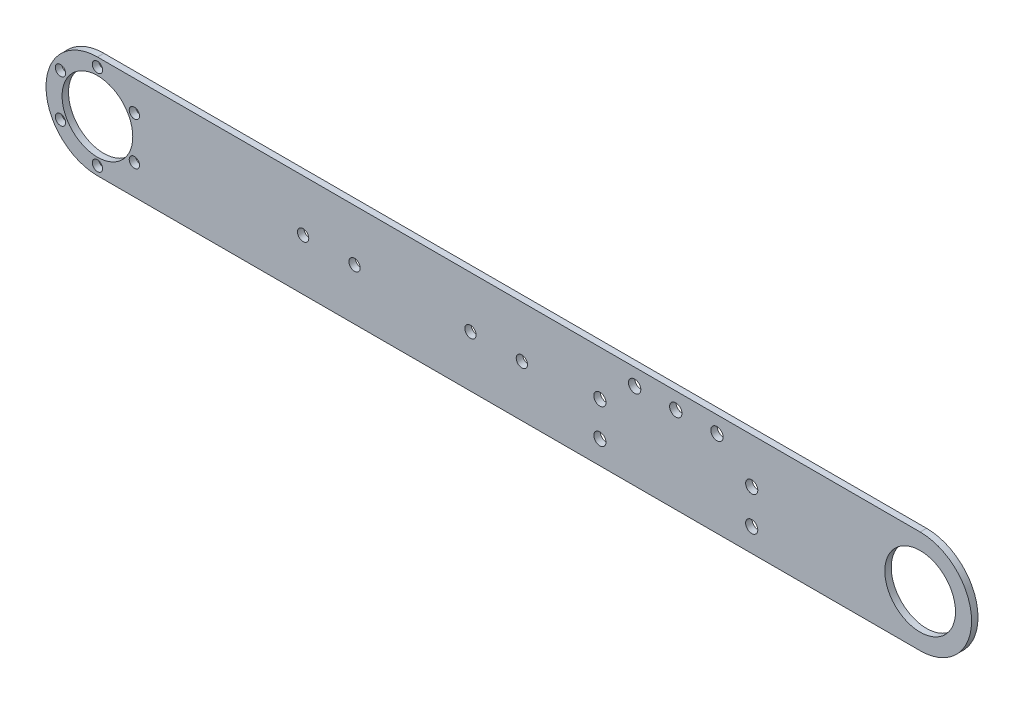
SolidWorks part; units mm, degrees
ref_plane "Front Plane" through (0, 0, 0) normal (0, 0, 1) x (1, 0, 0)
ref_plane "Top Plane" through (0, 0, 0) normal (0, 1, 0) x (1, 0, 0)
ref_plane "Right Plane" through (0, 0, 0) normal (1, 0, 0) x (0, 0, -1)
sketch "Sketch1" plane through (0, 0, 0) normal (0, 0, 1) x (1, 0, 0)
  line L1 (0, 0) -> (406.4, 0)
  line L3 (0, 50.8) -> (406.4, 50.8)
  arc A0 (0, 50.8) -> (0, 0) centre (0, 25.4) ccw
  arc A1 (406.4, 0) -> (406.4, 50.8) centre (406.4, 25.4) ccw
  dimension "D1" = 406.4
  dimension "D2" = 50.8
extrude "Boss-Extrude1" add sketch "Sketch1" along normal blind 3.175
sketch "Sketch2" plane through (0, 0, 3.175) normal (0, 0, 1) x (1, 0, 0)
  circle A0 centre (0, 25.4) radius 17.4625
  arc A1 (0, 50.8) -> (0, 0) centre (0, 25.4) ccw construction
  circle A3 centre (406.4, 25.4) radius 17.4625
  arc A5 (406.4, 0) -> (406.4, 50.8) centre (406.4, 25.4) ccw construction
  dimension "D1" = 34.925
  dimension "D2" = 34.925
extrude "Cut-Extrude1" cut sketch "Sketch2" against normal through all
sketch "Sketch4" plane through (0, 0, 3.175) normal (0, 0, 1) x (1, 0, 0)
  line L0 (0, 25.4) -> (368.5459, 25.4) construction
  circle A0 centre (101.6, 25.4) radius 2.794
  circle A1 centre (0, 25.4) radius 17.4625 construction
  circle A2 centre (127, 25.4) radius 2.794
  circle A3 centre (184.2729, 25.4) radius 2.794
  circle A4 centre (209.6729, 25.4) radius 2.794
  point P0 (0, 46.482)
  point P4 (0, 25.4)
  point P5 (18.2575, 35.941)
  point P7 (18.2575, 14.859)
  point P8 (0, 4.318)
  point P9 (-18.2575, 14.859)
  point P10 (-18.2575, 35.941)
  point P11 (0, 25.4)
  dimension "D3" = 5.588
  dimension "D4" = 101.6
  dimension "D5" = 25.4
  dimension "D6" = 5.588
  dimension "D7" = 25.4
  dimension "D1" = 21.082
  dimension "D2" = 6
hole_wizard "#10 Clearance Hole1" positions "3DSketch2" profile "Sketch5" hole size "#10" standard "ANSI Inch" end condition through all
sketch3d "3DSketch2"
  point P0 (18.2575, 35.941, 3.175)
  point P3 (18.2575, 14.859, 3.175)
  point P6 (0, 4.318, 3.175)
  point P9 (-18.2575, 14.859, 3.175)
  point P12 (-18.2575, 35.941, 3.175)
  point P15 (0, 46.482, 3.175)
sketch "Sketch5" plane through (18.2575, 35.941, 3.175) normal (1, 0, 0) x (0, -1, 0)
  line L0 (0, 0) -> (0, 3.175)
  line L1 (0, 3.175) -> (2.5527, 3.175)
  line L2 (2.5527, 3.175) -> (2.5527, 0)
  line L5 (2.5527, 0) -> (0, 0)
  line L11 (0, -6.35) -> (0, 107.95) construction
  dimension "Thru Hole Dia." = 5.1054
  dimension "Thru Hole Depth" = 3.175
ref_axis "Axis1" through (203.2, 50.8, 0) along (0, -0.9981, 0.0624)
ref_plane "Plane1" through (203.2, 0, 0) normal (1, 0, 0) x (0, 0, -1)
extrude "Cut-Extrude2" cut sketch "Sketch4" against normal through all
sketch "Sketch7" plane through (0, 0, 3.175) normal (0, 0, 1) x (1, 0, 0)
  line L0 (334.2879, 42.672) -> (260.3158, 42.672) construction
  line L1 (406.4, 50.8) -> (0, 50.8) construction
  circle A0 centre (306.0152, 42.672) radius 3.048
  circle A1 centre (285.6952, 42.672) radius 3.048
  circle A2 centre (265.3752, 42.672) radius 3.048
  dimension "D2" = 6.096
  dimension "D3" = 20.32
  dimension "D4" = 20.32
  dimension "D1" = 8.128
extrude "Cut-Extrude3" cut sketch "Sketch7" against normal through all
sketch "Sketch8" plane through (0, 0, 3.175) normal (0, 0, 1) x (1, 0, 0)
  circle A0 centre (323.1952, 11.5433) radius 3
  circle A1 centre (323.1952, 28.5433) radius 3
  circle A2 centre (248.1952, 11.5433) radius 3
  circle A3 centre (248.1952, 28.5433) radius 3
extrude "Cut-Extrude4" cut sketch "Sketch8" against normal through all
